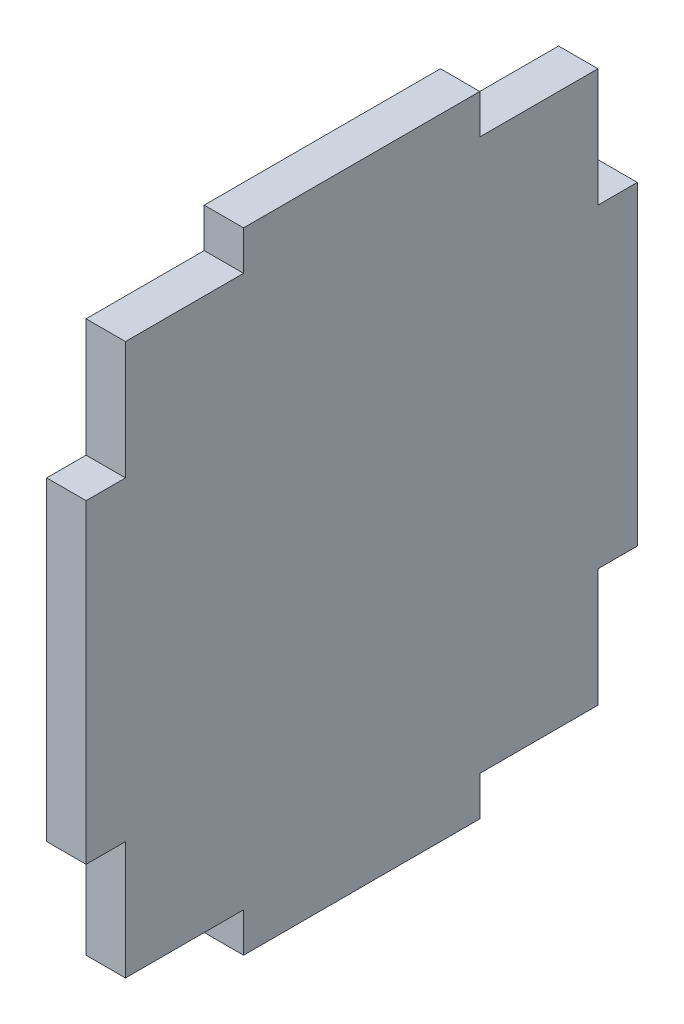
SolidWorks part; units mm, degrees
material "Acrylic (Medium-high impact)"
ref_plane "Front Plane" through (0, 0, 0) normal (0, 0, 1) x (1, 0, 0)
ref_plane "Top Plane" through (0, 0, 0) normal (0, 1, 0) x (1, 0, 0)
ref_plane "Right Plane" through (0, 0, 0) normal (1, 0, 0) x (0, 0, -1)
sketch "Sketch1" plane through (0, 0, 0) normal (1, 0, 0) x (0, 0, -1)
  line L1 (-35, -40) -> (35, -40)
  line L2 (-35, -40) -> (-35, 40)
  line L3 (-35, 40) -> (35, 40)
  line L4 (35, -40) -> (35, 40)
  line L5 (-35, -40) -> (35, 40) construction
  line L6 (-35, 40) -> (35, -40) construction
  point P0 (0, 0)
  dimension "D1" = 70
  dimension "D2" = 80
extrude "Boss-Extrude1" add sketch "Sketch1" along normal blind 5
sketch "Sketch3" plane through (5, 0, 0) normal (1, 0, 0) x (0, 0, -1)
  line L0 (-35, 20) -> (-30, 20)
  line L1 (-35, 40) -> (-35, -40) construction
  line L2 (-30, 20) -> (-30, 35)
  line L3 (-30, 35) -> (-15, 35)
  line L4 (-15, 35) -> (-15, 40)
  line L5 (35, 40) -> (-35, 40) construction
  line L6 (-15, 40) -> (-35, 40)
  line L7 (-35, 40) -> (-35, 20)
  dimension "D1" = 20
  dimension "D2" = 5
extrude "Cut-Extrude1" cut sketch "Sketch3" against normal through all both and the other way through all
mirror "Mirror1" about plane through (0, 0, 0) normal (0, 0, 1) of "Cut-Extrude1" second plane through (0, 0, 0) second plane normal (0, 1, 0)
